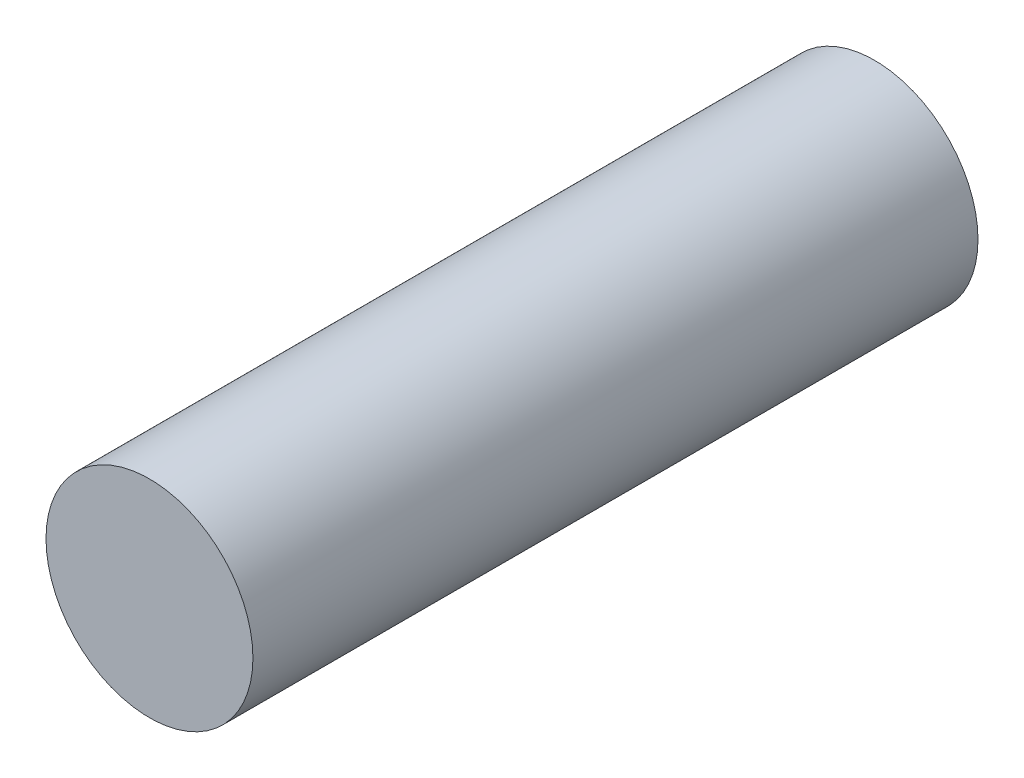
SolidWorks part; units mm, degrees
material "AISI 1020 Steel, Cold Rolled"
ref_plane "Front Plane" through (0, 0, 0) normal (0, 0, 1) x (1, 0, 0)
ref_plane "Top Plane" through (0, 0, 0) normal (0, 1, 0) x (1, 0, 0)
ref_plane "Right Plane" through (0, 0, 0) normal (1, 0, 0) x (0, 0, -1)
sketch "Sketch1" plane through (0, 0, 0) normal (0, 0, 1) x (1, 0, 0)
  circle A0 centre (0, 0) radius 6.35
  dimension "D1" = 12.7
extrude "Boss-Extrude1" add sketch "Sketch1" along normal blind 44.5
